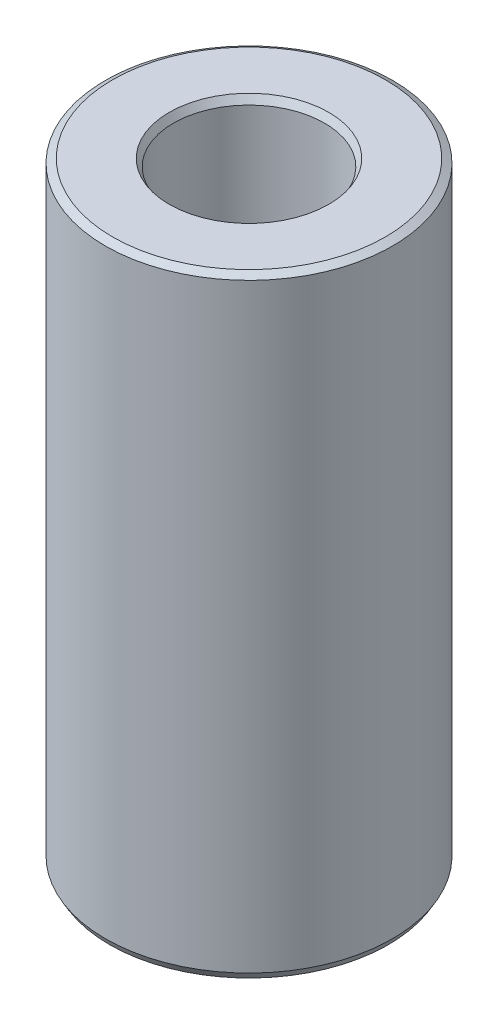
SolidWorks part; units mm, degrees
ref_plane "Front Plane" through (0, 0, 0) normal (0, 0, 1) x (1, 0, 0)
ref_plane "Top Plane" through (0, 0, 0) normal (0, 1, 0) x (1, 0, 0)
ref_plane "Right Plane" through (0, 0, 0) normal (1, 0, 0) x (0, 0, -1)
sketch "Sketch1" plane through (0, 0, 0) normal (0, 1, 0) x (1, 0, 0)
  circle A0 centre (0, 0) radius 35
  dimension "SLEEVE_OD" = 70
extrude "Boss-Extrude1" add sketch "Sketch1" along normal blind 149.0548
sketch "Sketch2" plane through (0, 0, 0) normal (0, 1, 0) x (1, 0, 0)
  circle A0 centre (0, 0) radius 18.4244
  dimension "BORE_D" = 36.8488
extrude "Cut-Extrude1" cut sketch "Sketch2" along normal through all
chamfer "Chamfer1" distance 1.0217 angle 60 4 edges at (0, 149.0548, 18.4244) (0, 0, 18.4244) (0, 0, 35) (0, 149.0548, 35) first distance on face at (0, 149.0548, 18.4244) first distance on face at (0, 0, 18.4244) first distance on face at (0, 149.0548, 35)
